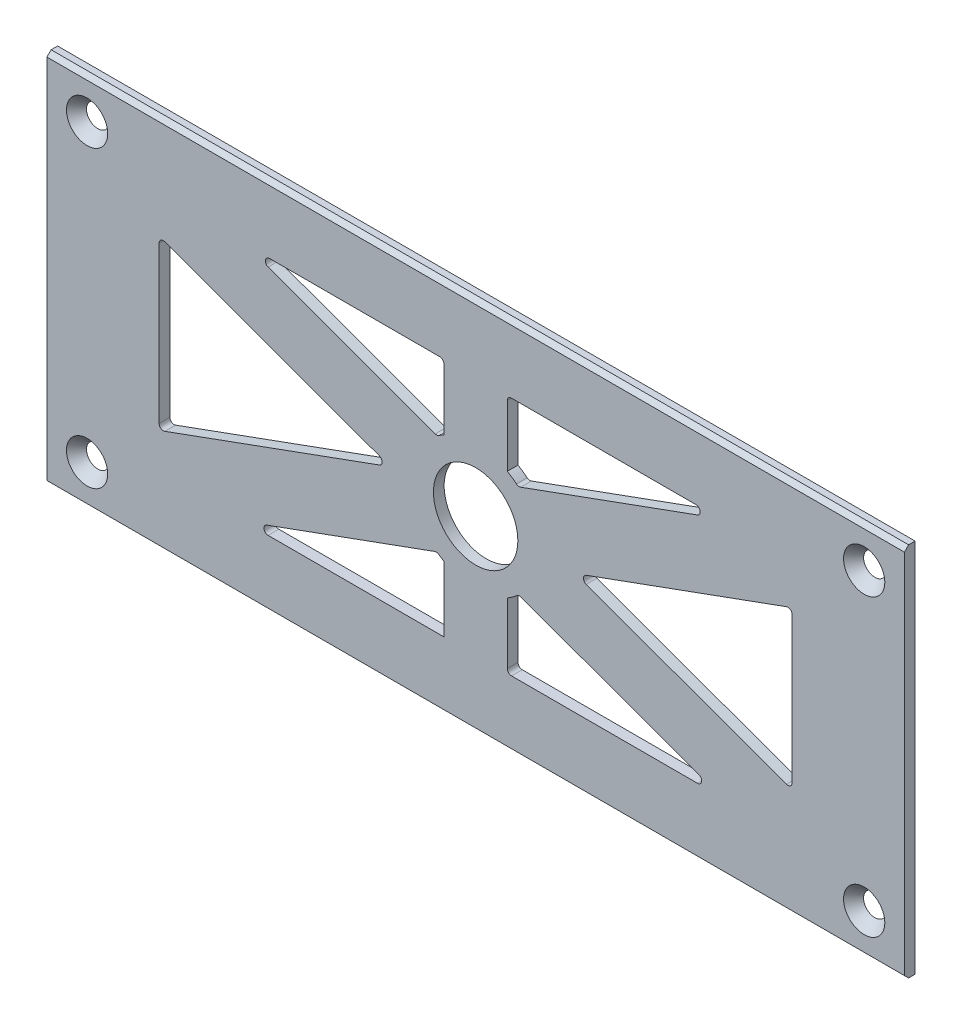
SolidWorks part; units mm, degrees
ref_plane "Front Plane" through (0, 0, 0) normal (0, 0, 1) x (1, 0, 0)
ref_plane "Top Plane" through (0, 0, 0) normal (0, 1, 0) x (1, 0, 0)
ref_plane "Right Plane" through (0, 0, 0) normal (1, 0, 0) x (0, 0, -1)
sketch "Sketch2" plane through (0, 0, 0) normal (0, 0, 1) x (1, 0, 0)
  line L1 (-101.6, -44.45) -> (101.6, -44.45)
  line L2 (-101.6, -44.45) -> (-101.6, 44.45)
  line L3 (-101.6, 44.45) -> (101.6, 44.45)
  line L4 (101.6, -44.45) -> (101.6, 44.45)
  line L5 (-101.6, -44.45) -> (101.6, 44.45) construction
  line L6 (-101.6, 44.45) -> (101.6, -44.45) construction
  circle A19 centre (0, 0) radius 10
  point P0 (0, 0)
  dimension "D6" = 20
  dimension "D2" = 88.9
  dimension "D4" = 203.2
extrude "Boss-Extrude1" add sketch "Sketch2" along normal mid plane 2.54
sketch "Sketch3" plane through (0, 0, 1.27) normal (0, 0, 1) x (1, 0, 0)
  line L0 (-101.6, 34.925) -> (-92.075, 34.925) construction
  line L1 (-101.6, 44.45) -> (-101.6, -44.45) construction
  line L2 (-92.075, 34.925) -> (-92.075, 44.45) construction
  line L3 (101.6, 44.45) -> (-101.6, 44.45) construction
  line L4 (92.075, 44.45) -> (92.075, 34.925) construction
  line L5 (92.075, 34.925) -> (101.6, 34.925) construction
  line L6 (101.6, -44.45) -> (101.6, 44.45) construction
  line L7 (92.075, -44.45) -> (92.075, -34.925) construction
  line L8 (-101.6, -44.45) -> (101.6, -44.45) construction
  line L9 (92.075, -34.925) -> (101.6, -34.925) construction
  line L10 (-92.075, -44.45) -> (-92.075, -34.925) construction
  line L11 (-92.075, -34.925) -> (-101.6, -34.925) construction
  circle A0 centre (-92.075, 34.925) radius 2.5527
  circle A1 centre (-92.075, -34.925) radius 2.5527
  circle A2 centre (92.075, -34.925) radius 2.5527
  circle A3 centre (92.075, 34.925) radius 2.5527
  dimension "D2" = 5.1054
  dimension "D1" = 9.525
extrude "Cut-Extrude1" cut sketch "Sketch3" against normal through all
hole_wizard "CSK for #10 Oval Head Machine Screw1" positions "Sketch5" profile "Sketch6" countersink size "#10" standard "ANSI Inch" end condition through all
sketch "Sketch5" plane through (0, 0, 1.27) normal (0, 0, 1) x (1, 0, 0)
  point P0 (-92.075, 34.925)
  point P3 (-92.075, -34.925)
  point P6 (92.075, -34.925)
  point P9 (92.075, 34.925)
sketch "Sketch6" plane through (-92.075, 34.925, 1.27) normal (1, 0, 0) x (0, -1, 0)
  line L0 (0, 0) -> (0, 2.54)
  line L1 (0, 2.54) -> (2.5527, 2.54)
  line L2 (2.5527, 2.54) -> (2.5527, 2.6882)
  line L3 (2.5527, 2.6882) -> (4.8895, 0)
  line L5 (4.8895, 0) -> (0, 0)
  line L6 (-2.5527, 2.6882) -> (-4.8895, 0) construction
  line L11 (0, -6.35) -> (0, 107.95) construction
  dimension "Thru Hole Dia." = 5.1054
  dimension "Thru Hole Depth" = 2.54
  dimension "Near C'Sink Dia." = 9.779
  dimension "Near C'Sink Angle" = 82
sketch "Sketch7" plane through (0, 0, 1.27) normal (0, 0, 1) x (1, 0, 0)
sketch "Sketch8" plane through (0, 0, 1.27) normal (0, 0, 1) x (1, 0, 0)
  line L0 (-7.5, 12.9904) -> (-7.5, 28.5)
  line L1 (-75, -28.5) -> (75, -28.5)
  line L2 (-75, -28.5) -> (-75, 28.5)
  line L3 (-75, 28.5) -> (75, 28.5)
  line L4 (75, -28.5) -> (75, 28.5)
  line L5 (-75, -28.5) -> (75, 28.5) construction
  line L6 (-75, 28.5) -> (75, -28.5) construction
  line L7 (7.5, 12.9904) -> (7.5, 28.5)
  line L8 (-9.057, 11.9571) -> (-54.5083, 28.5)
  line L9 (-75, 19.9957) -> (-14.881, -1.8858)
  line L10 (10.1873, -11.0099) -> (58.2408, -28.5)
  line L11 (14.6239, 3.3379) -> (75, -18.6372)
  line L12 (-9.1677, -11.8723) -> (-54.8518, -28.5)
  line L13 (-14.8638, 2.0171) -> (-75, -19.8707)
  line L14 (-7.5, -12.9904) -> (-7.5, -28.5)
  line L15 (7.5, -12.9904) -> (7.5, -28.5)
  line L16 (14.6543, -3.2018) -> (75, 18.7622)
  line L17 (10.0897, 11.0995) -> (57.8973, 28.5)
  line L18 (-7.5, -20.7452) -> (7.5, -20.7452)
  line L19 (0, -20.7452) -> (0, -15) construction
  line L20 (-44.9405, 9.0549) -> (-39.8102, 23.1503) construction
  line L21 (-32.0098, -20.1862) -> (-37.1401, -6.0908) construction
  circle A0 centre (0, 0) radius 15
  point P0 (0, 0)
  point P38 (-42.3753, 16.1026)
  point P41 (-34.5749, -13.1385)
  point P42 (67.6569, -28.5)
  dimension "D1" = 30
  dimension "D2" = 150
  dimension "D3" = 57
  dimension "D4" = 20
  dimension "D5" = 20
  dimension "D6" = 15
  dimension "D7" = 15
extrude "Cut-Extrude2" cut sketch "Sketch8" against normal blind 10 contours A0 L12 L1 L14 | A0 L15 L1 L10 | L16 L11 L4 | A0 L17 L3 L7 | A0 L0 L3 L8 | L13 L9 L2 region at (-23.2179, 22.8309, 1.27) region at (24.4329, 22.4776, 1.27) region at (-56.7447, 0.0625, 1.27) region at (57.8743, 0.0625, 1.27) region at (-23.3395, -22.7942, 1.27) region at (24.5577, -22.4427, 1.27)
fillet "Fillet1" radius 1 17 edges at (-54.8518, -28.5, 0) (7.5, -28.5, 0) (-9.1677, -11.8723, 0) (10.1873, -11.0099, 0) (58.2408, -28.5, 0) (75, -18.6372, 0) (75, 18.7622, 0) (23.623, 0.0625, 0) (57.8973, 28.5, 0) (7.5, 28.5, 0) (10.0897, 11.0995, 0) (-54.5083, 28.5, 0) (-7.5, 28.5, 0) (-9.057, 11.9571, 0) (-20.234, 0.0625, 0) (-75, -19.8707, 0) (-75, 19.9957, 0)
chamfer "Chamfer1" distance 1 angle 45 2 edges at (0, -44.45, 1.27) (0, 44.45, 1.27)
